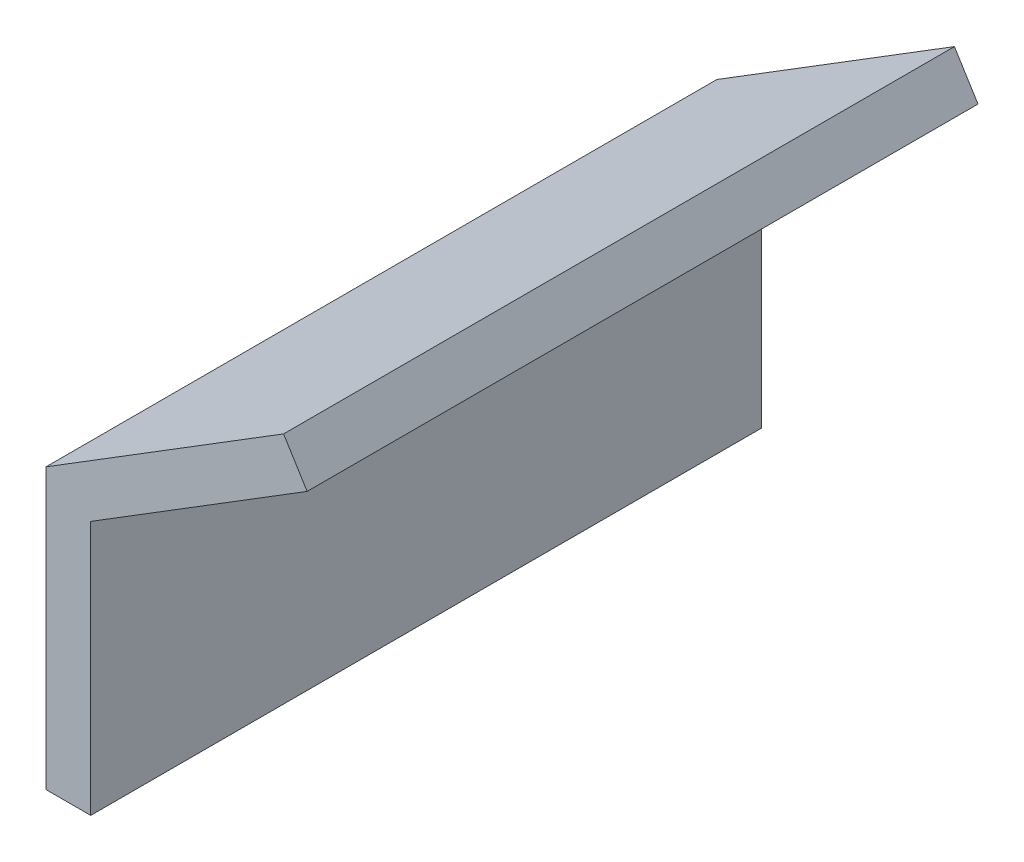
SolidWorks part; units mm, degrees
material "PLA"
ref_plane "Front Plane" through (0, 0, 0) normal (0, 0, 1) x (1, 0, 0)
ref_plane "Top Plane" through (0, 0, 0) normal (0, 1, 0) x (1, 0, 0)
ref_plane "Right Plane" through (0, 0, 0) normal (1, 0, 0) x (0, 0, -1)
sketch "Sketch1" plane through (0, 0, 0) normal (0, 0, 1) x (1, 0, 0)
  line L0 (0, 0) -> (42.4946, 26.3478)
  line L1 (0, 0) -> (0, -50)
  line L2 (8, -4.4527) -> (46.7103, 19.5486)
  line L3 (8, -4.4527) -> (8, -50)
  line L4 (42.4946, 26.3478) -> (46.7103, 19.5486)
  line L5 (0, -50) -> (8, -50)
  dimension "D1" = 50
  dimension "D2" = 50
  dimension "D3" = 121.8
  dimension "D4" = 8
extrude "Boss-Extrude1" add sketch "Sketch1" along normal mid plane 120
